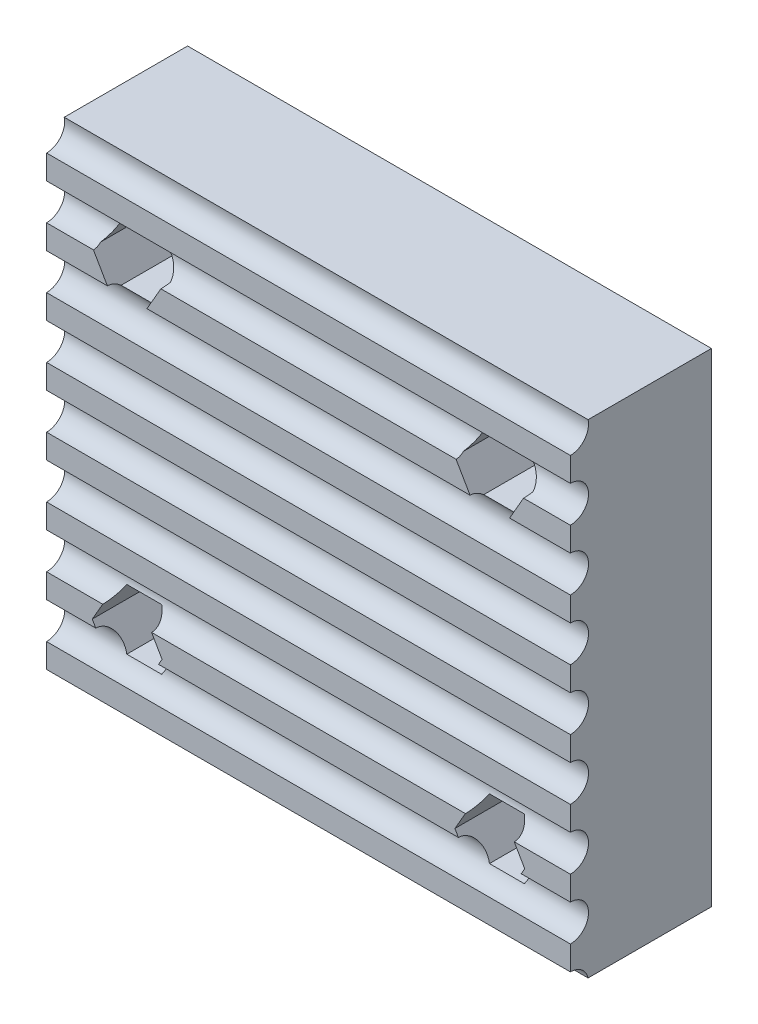
SolidWorks part; units mm, degrees
ref_plane "Front Plane" through (0, 0, 0) normal (0, 0, 1) x (1, 0, 0)
ref_plane "Top Plane" through (0, 0, 0) normal (0, 1, 0) x (1, 0, 0)
ref_plane "Right Plane" through (0, 0, 0) normal (1, 0, 0) x (0, 0, -1)
sketch "Sketch3" plane through (0, 0, 0) normal (0, 0, 1) x (1, 0, 0)
  line L0 (26, 0) -> (26, 24)
  line L1 (0, 0) -> (26, 0)
  line L2 (0, 0) -> (0, 24)
  line L3 (0, 24) -> (26, 24)
  line L4 (13, 0) -> (13, 24)
  line L6 (5.7321, 4) -> (4.866, 5.5)
  line L7 (4.866, 5.5) -> (3.134, 5.5)
  line L8 (3.134, 5.5) -> (2.2679, 4)
  line L9 (2.2679, 4) -> (3.134, 2.5)
  line L10 (3.134, 2.5) -> (4.866, 2.5)
  line L11 (4.866, 2.5) -> (5.7321, 4)
  line L12 (5.7321, 20) -> (4.866, 21.5)
  line L13 (4.866, 21.5) -> (3.134, 21.5)
  line L14 (3.134, 21.5) -> (2.2679, 20)
  line L15 (2.2679, 20) -> (3.134, 18.5)
  line L16 (3.134, 18.5) -> (4.866, 18.5)
  line L17 (4.866, 18.5) -> (5.7321, 20)
  line L18 (23.7321, 20) -> (22.866, 21.5)
  line L19 (22.866, 21.5) -> (21.134, 21.5)
  line L20 (21.134, 21.5) -> (20.2679, 20)
  line L21 (20.2679, 20) -> (21.134, 18.5)
  line L22 (21.134, 18.5) -> (22.866, 18.5)
  line L23 (22.866, 18.5) -> (23.7321, 20)
  line L24 (23.7321, 4) -> (22.866, 5.5)
  line L25 (22.866, 5.5) -> (21.134, 5.5)
  line L26 (21.134, 5.5) -> (20.2679, 4)
  line L27 (20.2679, 4) -> (21.134, 2.5)
  line L28 (21.134, 2.5) -> (22.866, 2.5)
  line L29 (22.866, 2.5) -> (23.7321, 4)
  circle A0 centre (4, 4) radius 1.5 construction
  circle A1 centre (4, 20) radius 1.5 construction
  circle A2 centre (22, 20) radius 1.5 construction
  circle A3 centre (22, 4) radius 1.5 construction
  dimension "D3" = 4
  dimension "D4" = 9
  dimension "D1" = 13
  dimension "D2" = 24
  dimension "D5" = 3
  dimension "D7" = 4
  dimension "D8" = 9
extrude "Boss-Extrude2" add sketch "Sketch3" along normal blind 7 contours L1 L4 L3 L2 | L4 L1 L0 L3 region at (19.3685, 12, 0) region at (6.6315, 12, 0)
sketch "Sketch5" [suppressed] plane through (26, 0, 0) normal (1, 0, 0) x (0, 0, -1)
  line L0 (-10, 24) -> (-10, 21)
  line L1 (-10, 0) -> (-10, 24) construction
  line L2 (-10, 21) -> (-8, 21)
  line L3 (-8, 21) -> (-8, 19)
  line L4 (-8, 19) -> (-10, 19)
  line L5 (-10, 19) -> (-10, 16)
  line L6 (-10, 16) -> (-8, 16)
  line L7 (-8, 16) -> (-8, 14)
  line L8 (-8, 14) -> (-10, 14)
  line L9 (-10, 14) -> (-10, 11)
  line L10 (-10, 11) -> (-8, 11)
  line L11 (-8, 11) -> (-8, 9)
  line L12 (-8, 9) -> (-10, 9)
  line L13 (-10, 9) -> (-10, 6)
  line L14 (-10, 6) -> (-8, 6)
  line L15 (-8, 6) -> (-8, 4)
  line L16 (-8, 4) -> (-10, 4)
  line L17 (-10, 4) -> (-10, 1)
  line L18 (-10, 1) -> (-8, 1)
  line L19 (-8, 1) -> (-8, -1)
  line L20 (-8, -1) -> (-10, -1)
  line L21 (-10, -1) -> (-10, -4)
  line L22 (-10, -4) -> (-8, -4)
  line L23 (-8, -4) -> (-8, -6)
  line L24 (-8, -6) -> (-10, -6)
  line L25 (-10, 24) -> (-12.9303, 24)
  line L26 (-12.9303, 24) -> (-12.9303, -6)
  line L27 (-12.9303, -6) -> (-10, -6)
  line L28 (-8, -6) -> (-10, -6)
  dimension "D1" = 3
  dimension "D2" = 2
  dimension "D3" = 2
  dimension "D4" = 6
sketch "Sketch7" plane through (26, 0, 0) normal (1, 0, 0) x (0, 0, -1)
  line L0 (-7, 0) -> (-7, 24) construction
  circle A0 centre (-7, 23.8) radius 0.9
  circle A1 centre (-7, 20.8) radius 0.9
  circle A2 centre (-7, 17.8) radius 0.9
  circle A3 centre (-7, 14.8) radius 0.9
  circle A4 centre (-7, 11.8) radius 0.9
  circle A5 centre (-7, 8.8) radius 0.9
  circle A6 centre (-7, 5.8) radius 0.9
  circle A7 centre (-7, 2.8) radius 0.9
  circle A8 centre (-7, -0.2) radius 0.9
  dimension "D1" = 1.8
  dimension "D2" = 0.2
  dimension "D3" = 9
extrude "Cut-Extrude1" cut sketch "Sketch7" against normal through all
sketch "Sketch8" plane through (0, 0, 0) normal (0, 0, -1) x (-1, 0, 0)
  line L0 (-3.134, 5.5) -> (-4.866, 2.5) construction
  line L1 (-21.134, 21.5) -> (-22.866, 18.5) construction
  point P4 (-4, 4)
  point P9 (-22, 20)
